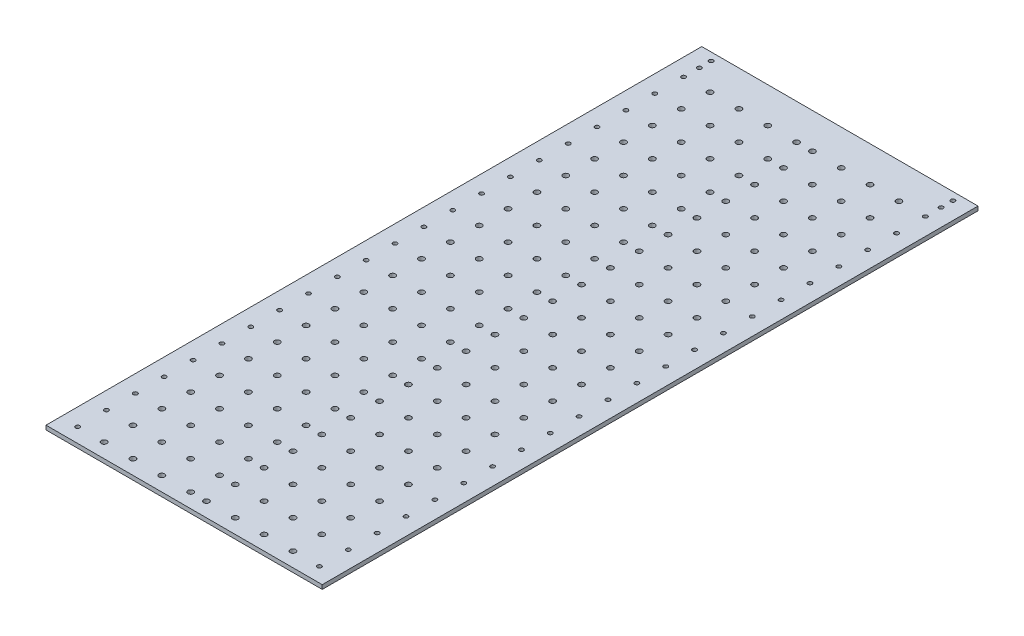
SolidWorks part; units mm, degrees
ref_plane "Front Plane" through (0, 0, 0) normal (0, 0, 1) x (1, 0, 0)
ref_plane "Top Plane" through (0, 0, 0) normal (0, 1, 0) x (1, 0, 0)
ref_plane "Right Plane" through (0, 0, 0) normal (1, 0, 0) x (0, 0, -1)
sketch "Sketch1" plane through (0, 0, 0) normal (0, 1, 0) x (1, 0, 0)
  line L0 (0, 250) -> (0, -250) construction
  line L1 (-105.305, -250) -> (105.305, -250)
  line L2 (-105.305, -250) -> (-105.305, 250)
  line L3 (-105.305, 250) -> (105.305, 250)
  line L4 (105.305, -250) -> (105.305, 250)
  line L5 (-105.305, -250) -> (105.305, 250) construction
  line L6 (-105.305, 250) -> (105.305, -250) construction
  circle A0 centre (92.18, 244) radius 1.6
  circle A1 centre (92.18, 235) radius 1.6
  circle A2 centre (92.18, 223) radius 1.6
  circle A3 centre (92.18, 201) radius 1.6
  circle A4 centre (92.18, 179) radius 1.6
  circle A5 centre (92.18, 157) radius 1.6
  circle A6 centre (92.18, 135) radius 1.6
  circle A7 centre (92.18, 113) radius 1.6
  circle A8 centre (92.18, 91) radius 1.6
  circle A9 centre (92.18, 69) radius 1.6
  circle A10 centre (92.18, 47) radius 1.6
  circle A11 centre (92.18, 25) radius 1.6
  circle A12 centre (92.18, 3) radius 1.6
  circle A13 centre (92.18, -19) radius 1.6
  circle A14 centre (92.18, -41) radius 1.6
  circle A15 centre (92.18, -63) radius 1.6
  circle A16 centre (92.18, -85) radius 1.6
  circle A17 centre (92.18, -107) radius 1.6
  circle A18 centre (92.18, -129) radius 1.6
  circle A19 centre (92.18, -151) radius 1.6
  circle A20 centre (92.18, -173) radius 1.6
  circle A21 centre (92.18, -195) radius 1.6
  circle A22 centre (92.18, -217) radius 1.6
  circle A23 centre (92.18, -239) radius 1.6
  circle A24 centre (-92.18, 69) radius 1.6
  circle A25 centre (-92.18, 91) radius 1.6
  circle A26 centre (-92.18, 113) radius 1.6
  circle A27 centre (-92.18, 135) radius 1.6
  circle A28 centre (-92.18, 157) radius 1.6
  circle A29 centre (-92.18, 179) radius 1.6
  circle A30 centre (-92.18, 201) radius 1.6
  circle A31 centre (-92.18, 223) radius 1.6
  circle A32 centre (-92.18, 235) radius 1.6
  circle A33 centre (-92.18, -239) radius 1.6
  circle A34 centre (-92.18, -217) radius 1.6
  circle A35 centre (-92.18, -195) radius 1.6
  circle A36 centre (-92.18, -173) radius 1.6
  circle A37 centre (-92.18, -151) radius 1.6
  circle A38 centre (-92.18, -129) radius 1.6
  circle A39 centre (-92.18, -107) radius 1.6
  circle A40 centre (-92.18, -85) radius 1.6
  circle A41 centre (-92.18, -63) radius 1.6
  circle A42 centre (-92.18, -41) radius 1.6
  circle A43 centre (-92.18, -19) radius 1.6
  circle A44 centre (-92.18, 3) radius 1.6
  circle A45 centre (-92.18, 25) radius 1.6
  circle A46 centre (-92.18, 47) radius 1.6
  circle A47 centre (-92.18, 244) radius 1.6
  circle A48 centre (6, -239) radius 2.125
  circle A49 centre (28, -239) radius 2.125
  circle A50 centre (50, -239) radius 2.125
  circle A51 centre (72, -239) radius 2.125
  circle A52 centre (28, -217) radius 2.125
  circle A53 centre (50, -217) radius 2.125
  circle A54 centre (72, -217) radius 2.125
  circle A55 centre (28, -195) radius 2.125
  circle A56 centre (50, -195) radius 2.125
  circle A57 centre (72, -195) radius 2.125
  circle A58 centre (28, -173) radius 2.125
  circle A59 centre (50, -173) radius 2.125
  circle A60 centre (72, -173) radius 2.125
  circle A61 centre (28, -151) radius 2.125
  circle A62 centre (50, -151) radius 2.125
  circle A63 centre (72, -151) radius 2.125
  circle A64 centre (28, -129) radius 2.125
  circle A65 centre (50, -129) radius 2.125
  circle A66 centre (72, -129) radius 2.125
  circle A67 centre (28, -107) radius 2.125
  circle A68 centre (50, -107) radius 2.125
  circle A69 centre (72, -107) radius 2.125
  circle A70 centre (28, -85) radius 2.125
  circle A71 centre (50, -85) radius 2.125
  circle A72 centre (72, -85) radius 2.125
  circle A73 centre (28, -63) radius 2.125
  circle A74 centre (50, -63) radius 2.125
  circle A75 centre (72, -63) radius 2.125
  circle A76 centre (28, -41) radius 2.125
  circle A77 centre (50, -41) radius 2.125
  circle A78 centre (72, -41) radius 2.125
  circle A79 centre (28, -19) radius 2.125
  circle A80 centre (50, -19) radius 2.125
  circle A81 centre (72, -19) radius 2.125
  circle A82 centre (28, 3) radius 2.125
  circle A83 centre (50, 3) radius 2.125
  circle A84 centre (72, 3) radius 2.125
  circle A85 centre (28, 25) radius 2.125
  circle A86 centre (50, 25) radius 2.125
  circle A87 centre (72, 25) radius 2.125
  circle A88 centre (28, 47) radius 2.125
  circle A89 centre (50, 47) radius 2.125
  circle A90 centre (72, 47) radius 2.125
  circle A91 centre (28, 69) radius 2.125
  circle A92 centre (50, 69) radius 2.125
  circle A93 centre (72, 69) radius 2.125
  circle A94 centre (28, 91) radius 2.125
  circle A95 centre (50, 91) radius 2.125
  circle A96 centre (72, 91) radius 2.125
  circle A97 centre (28, 113) radius 2.125
  circle A98 centre (50, 113) radius 2.125
  circle A99 centre (72, 113) radius 2.125
  circle A100 centre (28, 135) radius 2.125
  circle A101 centre (50, 135) radius 2.125
  circle A102 centre (72, 135) radius 2.125
  circle A103 centre (28, 157) radius 2.125
  circle A104 centre (50, 157) radius 2.125
  circle A105 centre (72, 157) radius 2.125
  circle A106 centre (28, 179) radius 2.125
  circle A107 centre (50, 179) radius 2.125
  circle A108 centre (72, 179) radius 2.125
  circle A109 centre (28, 201) radius 2.125
  circle A110 centre (50, 201) radius 2.125
  circle A111 centre (72, 201) radius 2.125
  circle A112 centre (28, 223) radius 2.125
  circle A113 centre (50, 223) radius 2.125
  circle A114 centre (72, 223) radius 2.125
  circle A115 centre (6, -217) radius 2.125
  circle A116 centre (6, -195) radius 2.125
  circle A117 centre (6, -173) radius 2.125
  circle A118 centre (6, -151) radius 2.125
  circle A119 centre (6, -129) radius 2.125
  circle A120 centre (6, -107) radius 2.125
  circle A121 centre (6, -85) radius 2.125
  circle A122 centre (6, -63) radius 2.125
  circle A123 centre (6, -41) radius 2.125
  circle A124 centre (6, -19) radius 2.125
  circle A125 centre (6, 3) radius 2.125
  circle A126 centre (6, 25) radius 2.125
  circle A127 centre (6, 47) radius 2.125
  circle A128 centre (6, 69) radius 2.125
  circle A129 centre (6, 91) radius 2.125
  circle A130 centre (6, 113) radius 2.125
  circle A131 centre (6, 135) radius 2.125
  circle A132 centre (6, 157) radius 2.125
  circle A133 centre (6, 179) radius 2.125
  circle A134 centre (6, 201) radius 2.125
  circle A135 centre (6, 223) radius 2.125
  circle A136 centre (-6, 223) radius 2.125
  circle A137 centre (-6, 201) radius 2.125
  circle A138 centre (-6, 179) radius 2.125
  circle A139 centre (-6, 157) radius 2.125
  circle A140 centre (-6, 135) radius 2.125
  circle A141 centre (-6, 113) radius 2.125
  circle A142 centre (-6, 91) radius 2.125
  circle A143 centre (-6, 69) radius 2.125
  circle A144 centre (-6, 47) radius 2.125
  circle A145 centre (-6, 25) radius 2.125
  circle A146 centre (-6, 3) radius 2.125
  circle A147 centre (-6, -19) radius 2.125
  circle A148 centre (-6, -41) radius 2.125
  circle A149 centre (-6, -63) radius 2.125
  circle A150 centre (-6, -85) radius 2.125
  circle A151 centre (-6, -107) radius 2.125
  circle A152 centre (-6, -129) radius 2.125
  circle A153 centre (-6, -151) radius 2.125
  circle A154 centre (-6, -173) radius 2.125
  circle A155 centre (-6, -195) radius 2.125
  circle A156 centre (-6, -217) radius 2.125
  circle A157 centre (-72, 223) radius 2.125
  circle A158 centre (-50, 223) radius 2.125
  circle A159 centre (-28, 223) radius 2.125
  circle A160 centre (-72, 201) radius 2.125
  circle A161 centre (-50, 201) radius 2.125
  circle A162 centre (-28, 201) radius 2.125
  circle A163 centre (-72, 179) radius 2.125
  circle A164 centre (-50, 179) radius 2.125
  circle A165 centre (-28, 179) radius 2.125
  circle A166 centre (-72, 157) radius 2.125
  circle A167 centre (-50, 157) radius 2.125
  circle A168 centre (-28, 157) radius 2.125
  circle A169 centre (-72, 135) radius 2.125
  circle A170 centre (-50, 135) radius 2.125
  circle A171 centre (-28, 135) radius 2.125
  circle A172 centre (-72, 113) radius 2.125
  circle A173 centre (-50, 113) radius 2.125
  circle A174 centre (-28, 113) radius 2.125
  circle A175 centre (-72, 91) radius 2.125
  circle A176 centre (-50, 91) radius 2.125
  circle A177 centre (-28, 91) radius 2.125
  circle A178 centre (-72, 69) radius 2.125
  circle A179 centre (-50, 69) radius 2.125
  circle A180 centre (-28, 69) radius 2.125
  circle A181 centre (-72, 47) radius 2.125
  circle A182 centre (-50, 47) radius 2.125
  circle A183 centre (-28, 47) radius 2.125
  circle A184 centre (-72, 25) radius 2.125
  circle A185 centre (-50, 25) radius 2.125
  circle A186 centre (-28, 25) radius 2.125
  circle A187 centre (-72, 3) radius 2.125
  circle A188 centre (-50, 3) radius 2.125
  circle A189 centre (-28, 3) radius 2.125
  circle A190 centre (-72, -19) radius 2.125
  circle A191 centre (-50, -19) radius 2.125
  circle A192 centre (-28, -19) radius 2.125
  circle A193 centre (-72, -41) radius 2.125
  circle A194 centre (-50, -41) radius 2.125
  circle A195 centre (-28, -41) radius 2.125
  circle A196 centre (-72, -63) radius 2.125
  circle A197 centre (-50, -63) radius 2.125
  circle A198 centre (-28, -63) radius 2.125
  circle A199 centre (-72, -85) radius 2.125
  circle A200 centre (-50, -85) radius 2.125
  circle A201 centre (-28, -85) radius 2.125
  circle A202 centre (-72, -107) radius 2.125
  circle A203 centre (-50, -107) radius 2.125
  circle A204 centre (-28, -107) radius 2.125
  circle A205 centre (-72, -129) radius 2.125
  circle A206 centre (-50, -129) radius 2.125
  circle A207 centre (-28, -129) radius 2.125
  circle A208 centre (-72, -151) radius 2.125
  circle A209 centre (-50, -151) radius 2.125
  circle A210 centre (-28, -151) radius 2.125
  circle A211 centre (-72, -173) radius 2.125
  circle A212 centre (-50, -173) radius 2.125
  circle A213 centre (-28, -173) radius 2.125
  circle A214 centre (-72, -195) radius 2.125
  circle A215 centre (-50, -195) radius 2.125
  circle A216 centre (-28, -195) radius 2.125
  circle A217 centre (-72, -217) radius 2.125
  circle A218 centre (-50, -217) radius 2.125
  circle A219 centre (-28, -217) radius 2.125
  circle A220 centre (-72, -239) radius 2.125
  circle A221 centre (-50, -239) radius 2.125
  circle A222 centre (-28, -239) radius 2.125
  circle A223 centre (-6, -239) radius 2.125
  point P0 (0, 0)
  dimension "D3" = 3.2
  dimension "D8" = 3.2
  dimension "D9" = 3.2
  dimension "D11" = 4.25
  dimension "D1" = 210.61
  dimension "D2" = 500
  dimension "D4" = 13.125
  dimension "D5" = 6
  dimension "D6" = 9
  dimension "D7" = 12
  dimension "D12" = 6
  dimension "D10" = 22
  dimension "D13" = 4
  dimension "D14" = 22
extrude "Boss-Extrude1" add sketch "Sketch1" along normal blind 3.175
equation "\"m3\"=3.2"
equation "\"D3@Sketch1\"=\"m3\""
equation "\"D8@Sketch1\"=\"m3\""
equation "\"D9@Sketch1\"=\"m3\""
